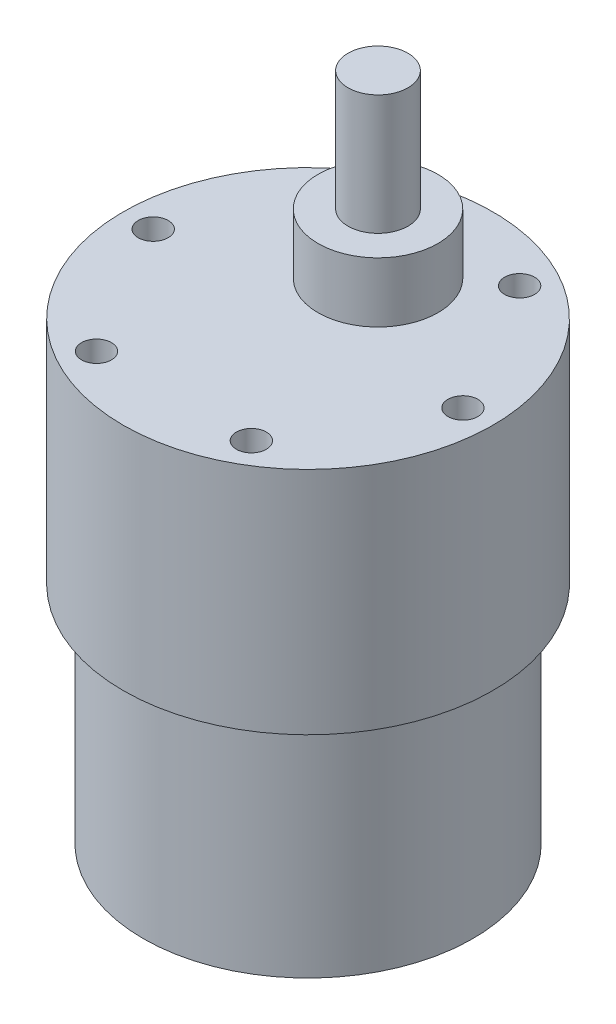
SolidWorks part; units mm, degrees
ref_plane "前视基准面" through (0, 0, 0) normal (0, 0, 1) x (1, 0, 0)
ref_plane "上视基准面" through (0, 0, 0) normal (0, 1, 0) x (1, 0, 0)
ref_plane "右视基准面" through (0, 0, 0) normal (1, 0, 0) x (0, 0, -1)
sketch "草图1" plane through (0, 0, 0) normal (0, 1, 0) x (1, 0, 0)
  circle A0 centre (0, 0) radius 18.5
  dimension "D1" = 37
extrude "凸台-拉伸1" add sketch "草图1" against normal blind 23
sketch "草图3" plane through (0, -23, 0) normal (0, -1, 0) x (1, 0, 0)
  circle A0 centre (0, 0) radius 16.5
  dimension "D1" = 33
extrude "凸台-拉伸2" add sketch "草图3" along normal blind 22.5
sketch "草图4" plane through (0, 0, 0) normal (0, 1, 0) x (1, 0, 0)
  line L0 (0, 18.5) -> (0, 0) construction
  line L1 (7.75, 13.4234) -> (-7.75, 13.4234) construction
  circle A0 centre (0, 0) radius 15.5 construction
  circle A1 centre (7.75, 13.4234) radius 1.5
  circle A2 centre (15.5, 0) radius 1.5
  circle A3 centre (7.75, -13.4234) radius 1.5
  circle A4 centre (-7.75, -13.4234) radius 1.5
  circle A5 centre (-15.5, 0) radius 1.5
  circle A6 centre (-7.75, 13.4234) radius 1.5
  circle A7 centre (0, 0) radius 18.5 construction
  point P7 (0, 0)
  point P17 (0, 0)
  dimension "D1" = 31
  dimension "D2" = 3
  dimension "D3" = 6
extrude "切除-拉伸1" cut sketch "草图4" against normal blind 15
sketch "草图5" plane through (0, 0, 0) normal (0, 1, 0) x (1, 0, 0)
  circle A0 centre (0, 7) radius 6
  dimension "D1" = 12
  dimension "D2" = 7
extrude "凸台-拉伸3" add sketch "草图5" along normal blind 6
sketch "草图6" plane through (0, 6, 0) normal (0, 1, 0) x (1, 0, 0)
  circle A0 centre (0, 7) radius 3
  circle A1 centre (0, 7) radius 6 construction
  dimension "D1" = 6
extrude "凸台-拉伸4" add sketch "草图6" along normal blind 12
sketch "草图7" plane through (0, -45.5, 0) normal (0, -1, 0) x (1, 0, 0)
  circle A0 centre (0, 0) radius 7
  dimension "D1" = 14
extrude "凸台-拉伸5" add sketch "草图7" along normal blind 6.2
